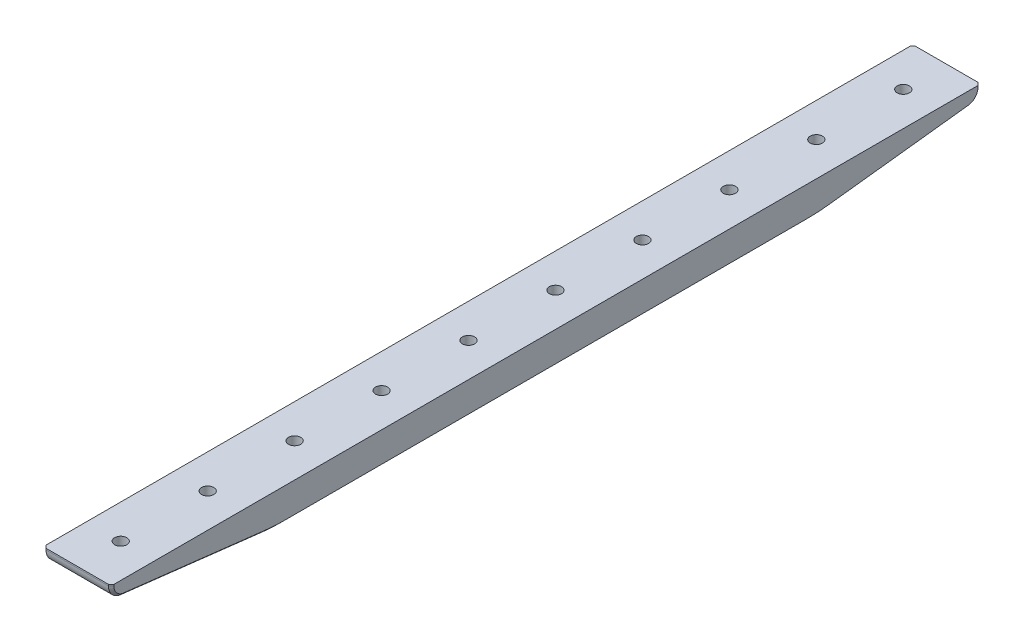
SolidWorks part; units mm, degrees
ref_plane "Front Plane" through (0, 0, 0) normal (0, 0, 1) x (1, 0, 0)
ref_plane "Top Plane" through (0, 0, 0) normal (0, 1, 0) x (1, 0, 0)
ref_plane "Right Plane" through (0, 0, 0) normal (1, 0, 0) x (0, 0, -1)
sketch "Sketch1" plane through (0, 0, 0) normal (1, 0, 0) x (0, 0, -1)
  line L0 (-160, 0) -> (160, 0)
  line L1 (0, 0) -> (0, -12) construction
  line L2 (-100, -12) -> (100, -12)
  line L3 (160, 0) -> (160, -5)
  line L4 (100, -12) -> (160, -5)
  line L5 (-100, -12) -> (-160, -5)
  line L6 (-160, 0) -> (-160, -5)
  dimension "D1" = 200
  dimension "D2" = 320
  dimension "D3" = 12
  dimension "D4" = 5
extrude "Boss-Extrude1" add sketch "Sketch1" along normal blind 25
fillet "Fillet1" radius 70 2 edges at (12.5, -12, -100) (12.5, -12, 100)
fillet "Fillet2" radius 5 2 edges at (12.5, -5, -160) (12.5, -5, 160)
chamfer "Chamfer1" distance 1 angle 45 18 edges at (0, -0.2747, -160) (0, -3.8738, -158.7348) (0, -8.5221, -129.8108) (0, -11.882, -99.9931) (0, -0.2747, 160) (0, -12, 0) (0, -3.8738, 158.7348) (0, -11.882, 99.9931) (0, -8.5221, 129.8108) (25, -0.2747, -160) (25, -3.8738, -158.7348) (25, -0.2747, 160) (25, -8.5221, -129.8108) (25, -3.8738, 158.7348) (25, -11.882, -99.9931) (25, -8.5221, 129.8108) (25, -11.882, 99.9931) (25, -12, 0)
sketch "Sketch2" plane through (0, -12, 0) normal (0, -1, 0) x (1, 0, 0)
  line L1 (1, 160) -> (24, 160) construction
  line L3 (0, 0) -> (25, 0) construction
  line L4 (25, 95.9305) -> (25, -95.9305) construction
  line L5 (12.5, 160) -> (12.5, 0) construction
  circle A0 centre (12.5, 144) radius 2.25
  circle A1 centre (12.5, 112) radius 2.25
  circle A2 centre (12.5, 48) radius 2.25
  circle A3 centre (12.5, 80) radius 2.25
  circle A4 centre (12.5, -80) radius 2.25
  circle A5 centre (12.5, -48) radius 2.25
  circle A6 centre (12.5, -112) radius 2.25
  circle A7 centre (12.5, -144) radius 2.25
  circle A8 centre (12.5, 16) radius 2.25
  circle A9 centre (12.5, -16) radius 2.25
  dimension "D2" = 32
  dimension "D3" = 32
  dimension "D4" = 32
  dimension "D5" = 4.5
  dimension "D7" = 32
  dimension "D1" = 16
  dimension "D6" = 12.5
extrude "Cut-Extrude1" cut sketch "Sketch2" against normal through all
sketch "Sketch5" plane through (0, 0, 160) normal (0, 0, 1) x (1, 0, 0)
  line L0 (24, 0) -> (1, 0) construction
  line L2 (24, -12) -> (1, -12) construction
  line L4 (8.5, -12) -> (16.5, -12)
  line L5 (8.5, -12) -> (8.5, -5)
  line L6 (8.5, -5) -> (16.5, -5)
  line L7 (16.5, -12) -> (16.5, -5)
  point P0 (12.5, -12)
  dimension "D1" = 5
  dimension "D2" = 8
extrude "Cut-Extrude2" cut sketch "Sketch5" against normal through all
chamfer "Chamfer2" distance 1 angle 45 14 edges at (16.5, -5.3339, -156.4521) (16.5, -5.3339, 156.4521) (16.5, -8.5221, -129.8108) (16.5, -8.5221, 129.8108) (16.5, -11.882, -99.9931) (16.5, -11.882, 99.9931) (16.5, -12, 0) (8.5, -5.3339, -156.4521) (8.5, -5.3339, 156.4521) (8.5, -8.5221, -129.8108) (8.5, -8.5221, 129.8108) (8.5, -11.882, -99.9931) (8.5, -11.882, 99.9931) (8.5, -12, 0)
